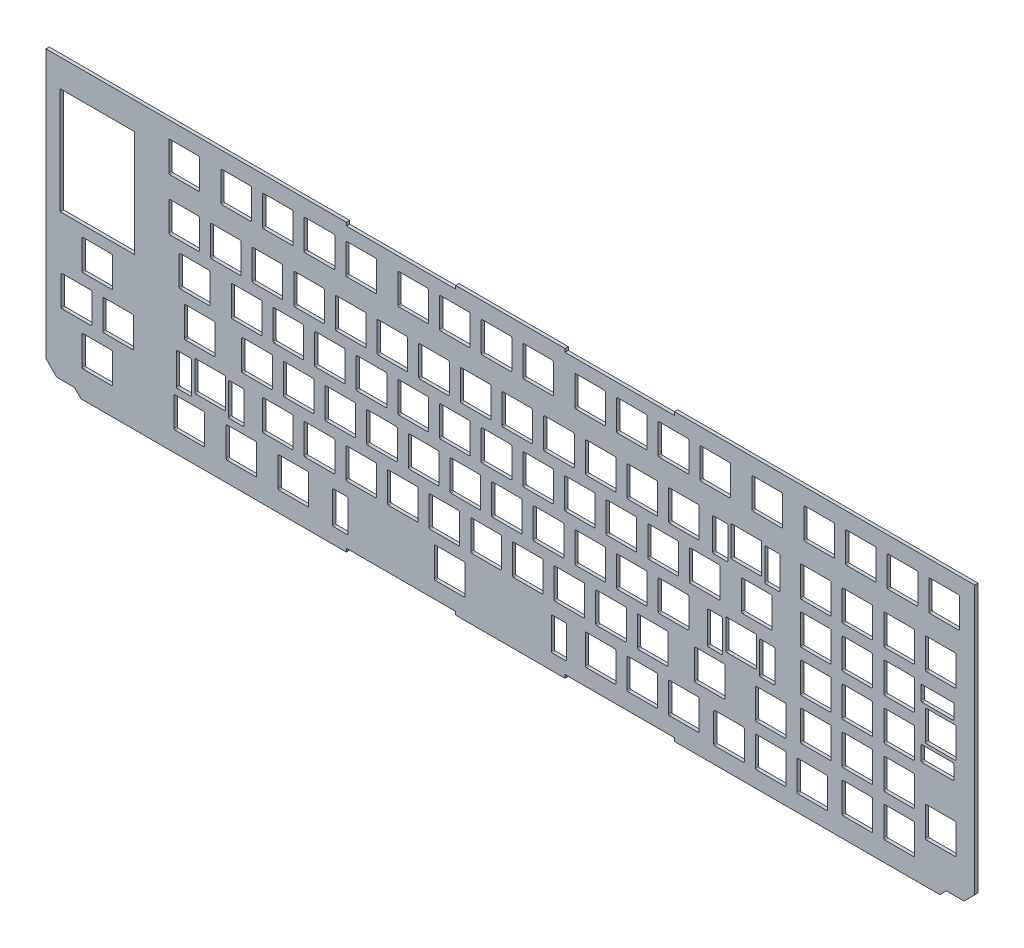
SolidWorks part; units mm, degrees
ref_plane "Přední rovina" through (0, 0, 0) normal (0, 0, 1) x (1, 0, 0)
ref_plane "Horní rovina" through (0, 0, 0) normal (0, 1, 0) x (1, 0, 0)
ref_plane "Pravá rovina" through (0, 0, 0) normal (1, 0, 0) x (0, 0, -1)
sketch "Model" plane through (0, 0, 0) normal (0, 0, 1) x (1, 0, 0)
  line L0 (53.8256, -2.525) -> (66.8256, -2.525)
  line L1 (53.8256, -16.525) -> (66.8256, -16.525)
  line L2 (53.3256, -3.025) -> (53.3256, -16.025)
  line L3 (67.3256, -3.025) -> (67.3256, -16.025)
  line L4 (77.6381, -2.525) -> (90.6381, -2.525)
  line L5 (77.6381, -16.525) -> (90.6381, -16.525)
  line L6 (77.1381, -3.025) -> (77.1381, -16.025)
  line L7 (91.1381, -3.025) -> (91.1381, -16.025)
  line L8 (96.6881, -2.525) -> (109.6881, -2.525)
  line L9 (96.6881, -16.525) -> (109.6881, -16.525)
  line L10 (96.1881, -3.025) -> (96.1881, -16.025)
  line L11 (110.1881, -3.025) -> (110.1881, -16.025)
  line L12 (115.7381, -2.525) -> (128.7381, -2.525)
  line L13 (115.7381, -16.525) -> (128.7381, -16.525)
  line L14 (115.2381, -3.025) -> (115.2381, -16.025)
  line L15 (129.2381, -3.025) -> (129.2381, -16.025)
  line L16 (134.7881, -2.525) -> (147.7881, -2.525)
  line L17 (134.7881, -16.525) -> (147.7881, -16.525)
  line L18 (134.2881, -3.025) -> (134.2881, -16.025)
  line L19 (148.2881, -3.025) -> (148.2881, -16.025)
  line L20 (158.6006, -2.525) -> (171.6006, -2.525)
  line L21 (158.6006, -16.525) -> (171.6006, -16.525)
  line L22 (158.1006, -3.025) -> (158.1006, -16.025)
  line L23 (172.1006, -3.025) -> (172.1006, -16.025)
  line L24 (177.6506, -2.525) -> (190.6506, -2.525)
  line L25 (177.6506, -16.525) -> (190.6506, -16.525)
  line L26 (177.1506, -3.025) -> (177.1506, -16.025)
  line L27 (191.1506, -3.025) -> (191.1506, -16.025)
  line L28 (196.7006, -2.525) -> (209.7006, -2.525)
  line L29 (196.7006, -16.525) -> (209.7006, -16.525)
  line L30 (196.2006, -3.025) -> (196.2006, -16.025)
  line L31 (210.2006, -3.025) -> (210.2006, -16.025)
  line L32 (215.7506, -2.525) -> (228.7506, -2.525)
  line L33 (215.7506, -16.525) -> (228.7506, -16.525)
  line L34 (215.2506, -3.025) -> (215.2506, -16.025)
  line L35 (229.2506, -3.025) -> (229.2506, -16.025)
  line L36 (239.5631, -2.525) -> (252.5631, -2.525)
  line L37 (239.5631, -16.525) -> (252.5631, -16.525)
  line L38 (239.0631, -3.025) -> (239.0631, -16.025)
  line L39 (253.0631, -3.025) -> (253.0631, -16.025)
  line L40 (258.6131, -2.525) -> (271.6131, -2.525)
  line L41 (258.6131, -16.525) -> (271.6131, -16.525)
  line L42 (258.1131, -3.025) -> (258.1131, -16.025)
  line L43 (272.1131, -3.025) -> (272.1131, -16.025)
  line L44 (277.6631, -2.525) -> (290.6631, -2.525)
  line L45 (277.6631, -16.525) -> (290.6631, -16.525)
  line L46 (277.1631, -3.025) -> (277.1631, -16.025)
  line L47 (291.1631, -3.025) -> (291.1631, -16.025)
  line L48 (296.7131, -2.525) -> (309.7131, -2.525)
  line L49 (296.7131, -16.525) -> (309.7131, -16.525)
  line L50 (296.2131, -3.025) -> (296.2131, -16.025)
  line L51 (310.2131, -3.025) -> (310.2131, -16.025)
  line L52 (320.5256, -2.525) -> (333.5256, -2.525)
  line L53 (320.5256, -16.525) -> (333.5256, -16.525)
  line L54 (320.0256, -3.025) -> (320.0256, -16.025)
  line L55 (334.0256, -3.025) -> (334.0256, -16.025)
  line L56 (344.3381, -2.525) -> (357.3381, -2.525)
  line L57 (344.3381, -16.525) -> (357.3381, -16.525)
  line L58 (343.8381, -3.025) -> (343.8381, -16.025)
  line L59 (357.8381, -3.025) -> (357.8381, -16.025)
  line L60 (363.3881, -2.525) -> (376.3881, -2.525)
  line L61 (363.3881, -16.525) -> (376.3881, -16.525)
  line L62 (362.8881, -3.025) -> (362.8881, -16.025)
  line L63 (376.8881, -3.025) -> (376.8881, -16.025)
  line L64 (382.4381, -2.525) -> (395.4381, -2.525)
  line L65 (382.4381, -16.525) -> (395.4381, -16.525)
  line L66 (381.9381, -3.025) -> (381.9381, -16.025)
  line L67 (395.9381, -3.025) -> (395.9381, -16.025)
  line L68 (401.4881, -2.525) -> (414.4881, -2.525)
  line L69 (401.4881, -16.525) -> (414.4881, -16.525)
  line L70 (400.9881, -3.025) -> (400.9881, -16.025)
  line L71 (414.9881, -3.025) -> (414.9881, -16.025)
  line L72 (53.8256, -26.3375) -> (66.8256, -26.3375)
  line L73 (53.8256, -40.3375) -> (66.8256, -40.3375)
  line L74 (53.3256, -26.8375) -> (53.3256, -39.8375)
  line L75 (67.3256, -26.8375) -> (67.3256, -39.8375)
  line L76 (72.8756, -26.3375) -> (85.8756, -26.3375)
  line L77 (72.8756, -40.3375) -> (85.8756, -40.3375)
  line L78 (72.3756, -26.8375) -> (72.3756, -39.8375)
  line L79 (86.3756, -26.8375) -> (86.3756, -39.8375)
  line L80 (91.9256, -26.3375) -> (104.9256, -26.3375)
  line L81 (91.9256, -40.3375) -> (104.9256, -40.3375)
  line L82 (91.4256, -26.8375) -> (91.4256, -39.8375)
  line L83 (105.4256, -26.8375) -> (105.4256, -39.8375)
  line L84 (110.9756, -26.3375) -> (123.9756, -26.3375)
  line L85 (110.9756, -40.3375) -> (123.9756, -40.3375)
  line L86 (110.4756, -26.8375) -> (110.4756, -39.8375)
  line L87 (124.4756, -26.8375) -> (124.4756, -39.8375)
  line L88 (130.0256, -26.3375) -> (143.0256, -26.3375)
  line L89 (130.0256, -40.3375) -> (143.0256, -40.3375)
  line L90 (129.5256, -26.8375) -> (129.5256, -39.8375)
  line L91 (143.5256, -26.8375) -> (143.5256, -39.8375)
  line L92 (149.0756, -26.3375) -> (162.0756, -26.3375)
  line L93 (149.0756, -40.3375) -> (162.0756, -40.3375)
  line L94 (148.5756, -26.8375) -> (148.5756, -39.8375)
  line L95 (162.5756, -26.8375) -> (162.5756, -39.8375)
  line L96 (168.1256, -26.3375) -> (181.1256, -26.3375)
  line L97 (168.1256, -40.3375) -> (181.1256, -40.3375)
  line L98 (167.6256, -26.8375) -> (167.6256, -39.8375)
  line L99 (181.6256, -26.8375) -> (181.6256, -39.8375)
  line L100 (187.1756, -26.3375) -> (200.1756, -26.3375)
  line L101 (187.1756, -40.3375) -> (200.1756, -40.3375)
  line L102 (186.6756, -26.8375) -> (186.6756, -39.8375)
  line L103 (200.6756, -26.8375) -> (200.6756, -39.8375)
  line L104 (206.2256, -26.3375) -> (219.2256, -26.3375)
  line L105 (206.2256, -40.3375) -> (219.2256, -40.3375)
  line L106 (205.7256, -26.8375) -> (205.7256, -39.8375)
  line L107 (219.7256, -26.8375) -> (219.7256, -39.8375)
  line L108 (225.2756, -26.3375) -> (238.2756, -26.3375)
  line L109 (225.2756, -40.3375) -> (238.2756, -40.3375)
  line L110 (224.7756, -26.8375) -> (224.7756, -39.8375)
  line L111 (238.7756, -26.8375) -> (238.7756, -39.8375)
  line L112 (244.3256, -26.3375) -> (257.3256, -26.3375)
  line L113 (244.3256, -40.3375) -> (257.3256, -40.3375)
  line L114 (243.8256, -26.8375) -> (243.8256, -39.8375)
  line L115 (257.8256, -26.8375) -> (257.8256, -39.8375)
  line L116 (263.3756, -26.3375) -> (276.3756, -26.3375)
  line L117 (263.3756, -40.3375) -> (276.3756, -40.3375)
  line L118 (262.8756, -26.8375) -> (262.8756, -39.8375)
  line L119 (276.8756, -26.8375) -> (276.8756, -39.8375)
  line L120 (282.4256, -26.3375) -> (295.4256, -26.3375)
  line L121 (282.4256, -40.3375) -> (295.4256, -40.3375)
  line L122 (281.9256, -26.8375) -> (281.9256, -39.8375)
  line L123 (295.9256, -26.8375) -> (295.9256, -39.8375)
  line L124 (311.0006, -26.3375) -> (324.0006, -26.3375)
  line L125 (311.0006, -40.3375) -> (324.0006, -40.3375)
  line L126 (310.5006, -26.8375) -> (310.5006, -39.8375)
  line L127 (324.5006, -26.8375) -> (324.5006, -39.8375)
  line L128 (302.5626, -27.3375) -> (308.5626, -27.3375)
  line L129 (302.5626, -42.3375) -> (308.5626, -42.3375)
  line L130 (302.0626, -27.8375) -> (302.0626, -41.8375)
  line L131 (309.0626, -27.8375) -> (309.0626, -41.8375)
  line L132 (326.4386, -27.3375) -> (332.4386, -27.3375)
  line L133 (326.4386, -42.3375) -> (332.4386, -42.3375)
  line L134 (325.9386, -27.8375) -> (325.9386, -41.8375)
  line L135 (332.9386, -27.8375) -> (332.9386, -41.8375)
  line L136 (342.7513, -26.3375) -> (355.7513, -26.3375)
  line L137 (342.7513, -40.3375) -> (355.7513, -40.3375)
  line L138 (342.2513, -26.8375) -> (342.2513, -39.8375)
  line L139 (356.2513, -26.8375) -> (356.2513, -39.8375)
  line L140 (361.8013, -26.3375) -> (374.8013, -26.3375)
  line L141 (361.8013, -40.3375) -> (374.8013, -40.3375)
  line L142 (361.3013, -26.8375) -> (361.3013, -39.8375)
  line L143 (375.3013, -26.8375) -> (375.3013, -39.8375)
  line L144 (380.8513, -26.3375) -> (393.8513, -26.3375)
  line L145 (380.8513, -40.3375) -> (393.8513, -40.3375)
  line L146 (380.3513, -26.8375) -> (380.3513, -39.8375)
  line L147 (394.3513, -26.8375) -> (394.3513, -39.8375)
  line L148 (399.9013, -26.3375) -> (412.9013, -26.3375)
  line L149 (399.9013, -40.3375) -> (412.9013, -40.3375)
  line L150 (399.4013, -26.8375) -> (399.4013, -39.8375)
  line L151 (413.4013, -26.8375) -> (413.4013, -39.8375)
  line L152 (58.5881, -45.3875) -> (71.5881, -45.3875)
  line L153 (58.5881, -59.3875) -> (71.5881, -59.3875)
  line L154 (58.0881, -45.8875) -> (58.0881, -58.8875)
  line L155 (72.0881, -45.8875) -> (72.0881, -58.8875)
  line L156 (82.4006, -45.3875) -> (95.4006, -45.3875)
  line L157 (82.4006, -59.3875) -> (95.4006, -59.3875)
  line L158 (81.9006, -45.8875) -> (81.9006, -58.8875)
  line L159 (95.9006, -45.8875) -> (95.9006, -58.8875)
  line L160 (101.4506, -45.3875) -> (114.4506, -45.3875)
  line L161 (101.4506, -59.3875) -> (114.4506, -59.3875)
  line L162 (100.9506, -45.8875) -> (100.9506, -58.8875)
  line L163 (114.9506, -45.8875) -> (114.9506, -58.8875)
  line L164 (120.5006, -45.3875) -> (133.5006, -45.3875)
  line L165 (120.5006, -59.3875) -> (133.5006, -59.3875)
  line L166 (120.0006, -45.8875) -> (120.0006, -58.8875)
  line L167 (134.0006, -45.8875) -> (134.0006, -58.8875)
  line L168 (139.5506, -45.3875) -> (152.5506, -45.3875)
  line L169 (139.5506, -59.3875) -> (152.5506, -59.3875)
  line L170 (139.0506, -45.8875) -> (139.0506, -58.8875)
  line L171 (153.0506, -45.8875) -> (153.0506, -58.8875)
  line L172 (158.6006, -45.3875) -> (171.6006, -45.3875)
  line L173 (158.6006, -59.3875) -> (171.6006, -59.3875)
  line L174 (158.1006, -45.8875) -> (158.1006, -58.8875)
  line L175 (172.1006, -45.8875) -> (172.1006, -58.8875)
  line L176 (177.6506, -45.3875) -> (190.6506, -45.3875)
  line L177 (177.6506, -59.3875) -> (190.6506, -59.3875)
  line L178 (177.1506, -45.8875) -> (177.1506, -58.8875)
  line L179 (191.1506, -45.8875) -> (191.1506, -58.8875)
  line L180 (196.7006, -45.3875) -> (209.7006, -45.3875)
  line L181 (196.7006, -59.3875) -> (209.7006, -59.3875)
  line L182 (196.2006, -45.8875) -> (196.2006, -58.8875)
  line L183 (210.2006, -45.8875) -> (210.2006, -58.8875)
  line L184 (215.7506, -45.3875) -> (228.7506, -45.3875)
  line L185 (215.7506, -59.3875) -> (228.7506, -59.3875)
  line L186 (215.2506, -45.8875) -> (215.2506, -58.8875)
  line L187 (229.2506, -45.8875) -> (229.2506, -58.8875)
  line L188 (234.8006, -45.3875) -> (247.8006, -45.3875)
  line L189 (234.8006, -59.3875) -> (247.8006, -59.3875)
  line L190 (234.3006, -45.8875) -> (234.3006, -58.8875)
  line L191 (248.3006, -45.8875) -> (248.3006, -58.8875)
  line L192 (253.8506, -45.3875) -> (266.8506, -45.3875)
  line L193 (253.8506, -59.3875) -> (266.8506, -59.3875)
  line L194 (253.3506, -45.8875) -> (253.3506, -58.8875)
  line L195 (267.3506, -45.8875) -> (267.3506, -58.8875)
  line L196 (272.9006, -45.3875) -> (285.9006, -45.3875)
  line L197 (272.9006, -59.3875) -> (285.9006, -59.3875)
  line L198 (272.4006, -45.8875) -> (272.4006, -58.8875)
  line L199 (286.4006, -45.8875) -> (286.4006, -58.8875)
  line L200 (291.9506, -45.3875) -> (304.9506, -45.3875)
  line L201 (291.9506, -59.3875) -> (304.9506, -59.3875)
  line L202 (291.4506, -45.8875) -> (291.4506, -58.8875)
  line L203 (305.4506, -45.8875) -> (305.4506, -58.8875)
  line L204 (315.7631, -45.3875) -> (328.7631, -45.3875)
  line L205 (315.7631, -59.3875) -> (328.7631, -59.3875)
  line L206 (315.2631, -45.8875) -> (315.2631, -58.8875)
  line L207 (329.2631, -45.8875) -> (329.2631, -58.8875)
  line L208 (342.7513, -45.3875) -> (355.7513, -45.3875)
  line L209 (342.7513, -59.3875) -> (355.7513, -59.3875)
  line L210 (342.2513, -45.8875) -> (342.2513, -58.8875)
  line L211 (356.2513, -45.8875) -> (356.2513, -58.8875)
  line L212 (361.8013, -45.3875) -> (374.8013, -45.3875)
  line L213 (361.8013, -59.3875) -> (374.8013, -59.3875)
  line L214 (361.3013, -45.8875) -> (361.3013, -58.8875)
  line L215 (375.3013, -45.8875) -> (375.3013, -58.8875)
  line L216 (380.8513, -45.3875) -> (393.8513, -45.3875)
  line L217 (380.8513, -59.3875) -> (393.8513, -59.3875)
  line L218 (380.3513, -45.8875) -> (380.3513, -58.8875)
  line L219 (394.3513, -45.8875) -> (394.3513, -58.8875)
  line L220 (413.4013, -55.4125) -> (413.4013, -68.4125)
  line L221 (399.4013, -55.4125) -> (399.4013, -68.4125)
  line L222 (412.9013, -54.9125) -> (399.9013, -54.9125)
  line L223 (412.9013, -68.9125) -> (399.9013, -68.9125)
  line L224 (412.4013, -46.9745) -> (412.4013, -52.9745)
  line L225 (397.4013, -46.9745) -> (397.4013, -52.9745)
  line L226 (411.9013, -46.4745) -> (397.9013, -46.4745)
  line L227 (411.9013, -53.4745) -> (397.9013, -53.4745)
  line L228 (412.4013, -70.8505) -> (412.4013, -76.8505)
  line L229 (397.4013, -70.8505) -> (397.4013, -76.8505)
  line L230 (411.9013, -70.3505) -> (397.9013, -70.3505)
  line L231 (411.9013, -77.3505) -> (397.9013, -77.3505)
  line L232 (14.1369, -61.2619) -> (27.1369, -61.2619)
  line L233 (14.1369, -75.2619) -> (27.1369, -75.2619)
  line L234 (13.6369, -61.7619) -> (13.6369, -74.7619)
  line L235 (27.6369, -61.7619) -> (27.6369, -74.7619)
  line L236 (60.9694, -64.4375) -> (73.9694, -64.4375)
  line L237 (60.9694, -78.4375) -> (73.9694, -78.4375)
  line L238 (60.4694, -64.9375) -> (60.4694, -77.9375)
  line L239 (74.4694, -64.9375) -> (74.4694, -77.9375)
  line L240 (87.1631, -64.4375) -> (100.1631, -64.4375)
  line L241 (87.1631, -78.4375) -> (100.1631, -78.4375)
  line L242 (86.6631, -64.9375) -> (86.6631, -77.9375)
  line L243 (100.6631, -64.9375) -> (100.6631, -77.9375)
  line L244 (106.2131, -64.4375) -> (119.2131, -64.4375)
  line L245 (106.2131, -78.4375) -> (119.2131, -78.4375)
  line L246 (105.7131, -64.9375) -> (105.7131, -77.9375)
  line L247 (119.7131, -64.9375) -> (119.7131, -77.9375)
  line L248 (125.2631, -64.4375) -> (138.2631, -64.4375)
  line L249 (125.2631, -78.4375) -> (138.2631, -78.4375)
  line L250 (124.7631, -64.9375) -> (124.7631, -77.9375)
  line L251 (138.7631, -64.9375) -> (138.7631, -77.9375)
  line L252 (144.3131, -64.4375) -> (157.3131, -64.4375)
  line L253 (144.3131, -78.4375) -> (157.3131, -78.4375)
  line L254 (143.8131, -64.9375) -> (143.8131, -77.9375)
  line L255 (157.8131, -64.9375) -> (157.8131, -77.9375)
  line L256 (163.3631, -64.4375) -> (176.3631, -64.4375)
  line L257 (163.3631, -78.4375) -> (176.3631, -78.4375)
  line L258 (162.8631, -64.9375) -> (162.8631, -77.9375)
  line L259 (176.8631, -64.9375) -> (176.8631, -77.9375)
  line L260 (182.4131, -64.4375) -> (195.4131, -64.4375)
  line L261 (182.4131, -78.4375) -> (195.4131, -78.4375)
  line L262 (181.9131, -64.9375) -> (181.9131, -77.9375)
  line L263 (195.9131, -64.9375) -> (195.9131, -77.9375)
  line L264 (201.4631, -64.4375) -> (214.4631, -64.4375)
  line L265 (201.4631, -78.4375) -> (214.4631, -78.4375)
  line L266 (200.9631, -64.9375) -> (200.9631, -77.9375)
  line L267 (214.9631, -64.9375) -> (214.9631, -77.9375)
  line L268 (220.5131, -64.4375) -> (233.5131, -64.4375)
  line L269 (220.5131, -78.4375) -> (233.5131, -78.4375)
  line L270 (220.0131, -64.9375) -> (220.0131, -77.9375)
  line L271 (234.0131, -64.9375) -> (234.0131, -77.9375)
  line L272 (239.5631, -64.4375) -> (252.5631, -64.4375)
  line L273 (239.5631, -78.4375) -> (252.5631, -78.4375)
  line L274 (239.0631, -64.9375) -> (239.0631, -77.9375)
  line L275 (253.0631, -64.9375) -> (253.0631, -77.9375)
  line L276 (258.6131, -64.4375) -> (271.6131, -64.4375)
  line L277 (258.6131, -78.4375) -> (271.6131, -78.4375)
  line L278 (258.1131, -64.9375) -> (258.1131, -77.9375)
  line L279 (272.1131, -64.9375) -> (272.1131, -77.9375)
  line L280 (277.6631, -64.4375) -> (290.6631, -64.4375)
  line L281 (277.6631, -78.4375) -> (290.6631, -78.4375)
  line L282 (277.1631, -64.9375) -> (277.1631, -77.9375)
  line L283 (291.1631, -64.9375) -> (291.1631, -77.9375)
  line L284 (308.6194, -64.4375) -> (321.6194, -64.4375)
  line L285 (308.6194, -78.4375) -> (321.6194, -78.4375)
  line L286 (308.1194, -64.9375) -> (308.1194, -77.9375)
  line L287 (322.1194, -64.9375) -> (322.1194, -77.9375)
  line L288 (300.1814, -65.4375) -> (306.1814, -65.4375)
  line L289 (300.1814, -80.4375) -> (306.1814, -80.4375)
  line L290 (299.6814, -65.9375) -> (299.6814, -79.9375)
  line L291 (306.6814, -65.9375) -> (306.6814, -79.9375)
  line L292 (324.0574, -65.4375) -> (330.0574, -65.4375)
  line L293 (324.0574, -80.4375) -> (330.0574, -80.4375)
  line L294 (323.5574, -65.9375) -> (323.5574, -79.9375)
  line L295 (330.5574, -65.9375) -> (330.5574, -79.9375)
  line L296 (342.7513, -64.4375) -> (355.7513, -64.4375)
  line L297 (342.7513, -78.4375) -> (355.7513, -78.4375)
  line L298 (342.2513, -64.9375) -> (342.2513, -77.9375)
  line L299 (356.2513, -64.9375) -> (356.2513, -77.9375)
  line L300 (361.8013, -64.4375) -> (374.8013, -64.4375)
  line L301 (361.8013, -78.4375) -> (374.8013, -78.4375)
  line L302 (361.3013, -64.9375) -> (361.3013, -77.9375)
  line L303 (375.3013, -64.9375) -> (375.3013, -77.9375)
  line L304 (380.8513, -64.4375) -> (393.8513, -64.4375)
  line L305 (380.8513, -78.4375) -> (393.8513, -78.4375)
  line L306 (380.3513, -64.9375) -> (380.3513, -77.9375)
  line L307 (394.3513, -64.9375) -> (394.3513, -77.9375)
  line L308 (4.6119, -80.3119) -> (17.6119, -80.3119)
  line L309 (4.6119, -94.3119) -> (17.6119, -94.3119)
  line L310 (4.1119, -80.8119) -> (4.1119, -93.8119)
  line L311 (18.1119, -80.8119) -> (18.1119, -93.8119)
  line L312 (23.6619, -80.3119) -> (36.6619, -80.3119)
  line L313 (23.6619, -94.3119) -> (36.6619, -94.3119)
  line L314 (23.1619, -80.8119) -> (23.1619, -93.8119)
  line L315 (37.1619, -80.8119) -> (37.1619, -93.8119)
  line L316 (65.7319, -83.4875) -> (78.7319, -83.4875)
  line L317 (65.7319, -97.4875) -> (78.7319, -97.4875)
  line L318 (65.2319, -83.9875) -> (65.2319, -96.9875)
  line L319 (79.2319, -83.9875) -> (79.2319, -96.9875)
  line L320 (57.2939, -84.4875) -> (63.2939, -84.4875)
  line L321 (57.2939, -99.4875) -> (63.2939, -99.4875)
  line L322 (56.7939, -84.9875) -> (56.7939, -98.9875)
  line L323 (63.7939, -84.9875) -> (63.7939, -98.9875)
  line L324 (81.1699, -84.4875) -> (87.1699, -84.4875)
  line L325 (81.1699, -99.4875) -> (87.1699, -99.4875)
  line L326 (80.6699, -84.9875) -> (80.6699, -98.9875)
  line L327 (87.6699, -84.9875) -> (87.6699, -98.9875)
  line L328 (96.6881, -83.4875) -> (109.6881, -83.4875)
  line L329 (96.6881, -97.4875) -> (109.6881, -97.4875)
  line L330 (96.1881, -83.9875) -> (96.1881, -96.9875)
  line L331 (110.1881, -83.9875) -> (110.1881, -96.9875)
  line L332 (115.7381, -83.4875) -> (128.7381, -83.4875)
  line L333 (115.7381, -97.4875) -> (128.7381, -97.4875)
  line L334 (115.2381, -83.9875) -> (115.2381, -96.9875)
  line L335 (129.2381, -83.9875) -> (129.2381, -96.9875)
  line L336 (134.7881, -83.4875) -> (147.7881, -83.4875)
  line L337 (134.7881, -97.4875) -> (147.7881, -97.4875)
  line L338 (134.2881, -83.9875) -> (134.2881, -96.9875)
  line L339 (148.2881, -83.9875) -> (148.2881, -96.9875)
  line L340 (153.8381, -83.4875) -> (166.8381, -83.4875)
  line L341 (153.8381, -97.4875) -> (166.8381, -97.4875)
  line L342 (153.3381, -83.9875) -> (153.3381, -96.9875)
  line L343 (167.3381, -83.9875) -> (167.3381, -96.9875)
  line L344 (172.8881, -83.4875) -> (185.8881, -83.4875)
  line L345 (172.8881, -97.4875) -> (185.8881, -97.4875)
  line L346 (172.3881, -83.9875) -> (172.3881, -96.9875)
  line L347 (186.3881, -83.9875) -> (186.3881, -96.9875)
  line L348 (191.9381, -83.4875) -> (204.9381, -83.4875)
  line L349 (191.9381, -97.4875) -> (204.9381, -97.4875)
  line L350 (191.4381, -83.9875) -> (191.4381, -96.9875)
  line L351 (205.4381, -83.9875) -> (205.4381, -96.9875)
  line L352 (210.9881, -83.4875) -> (223.9881, -83.4875)
  line L353 (210.9881, -97.4875) -> (223.9881, -97.4875)
  line L354 (210.4881, -83.9875) -> (210.4881, -96.9875)
  line L355 (224.4881, -83.9875) -> (224.4881, -96.9875)
  line L356 (230.0381, -83.4875) -> (243.0381, -83.4875)
  line L357 (230.0381, -97.4875) -> (243.0381, -97.4875)
  line L358 (229.5381, -83.9875) -> (229.5381, -96.9875)
  line L359 (243.5381, -83.9875) -> (243.5381, -96.9875)
  line L360 (249.0881, -83.4875) -> (262.0881, -83.4875)
  line L361 (249.0881, -97.4875) -> (262.0881, -97.4875)
  line L362 (248.5881, -83.9875) -> (248.5881, -96.9875)
  line L363 (262.5881, -83.9875) -> (262.5881, -96.9875)
  line L364 (268.1381, -83.4875) -> (281.1381, -83.4875)
  line L365 (268.1381, -97.4875) -> (281.1381, -97.4875)
  line L366 (267.6381, -83.9875) -> (267.6381, -96.9875)
  line L367 (281.6381, -83.9875) -> (281.6381, -96.9875)
  line L368 (294.3319, -83.4875) -> (307.3319, -83.4875)
  line L369 (294.3319, -97.4875) -> (307.3319, -97.4875)
  line L370 (293.8319, -83.9875) -> (293.8319, -96.9875)
  line L371 (307.8319, -83.9875) -> (307.8319, -96.9875)
  line L372 (342.7513, -83.4875) -> (355.7513, -83.4875)
  line L373 (342.7513, -97.4875) -> (355.7513, -97.4875)
  line L374 (342.2513, -83.9875) -> (342.2513, -96.9875)
  line L375 (356.2513, -83.9875) -> (356.2513, -96.9875)
  line L376 (361.8013, -83.4875) -> (374.8013, -83.4875)
  line L377 (361.8013, -97.4875) -> (374.8013, -97.4875)
  line L378 (361.3013, -83.9875) -> (361.3013, -96.9875)
  line L379 (375.3013, -83.9875) -> (375.3013, -96.9875)
  line L380 (380.8513, -83.4875) -> (393.8513, -83.4875)
  line L381 (380.8513, -97.4875) -> (393.8513, -97.4875)
  line L382 (380.3513, -83.9875) -> (380.3513, -96.9875)
  line L383 (394.3513, -83.9875) -> (394.3513, -96.9875)
  line L384 (413.4013, -93.5125) -> (413.4013, -106.5125)
  line L385 (399.4013, -93.5125) -> (399.4013, -106.5125)
  line L386 (412.9013, -93.0125) -> (399.9013, -93.0125)
  line L387 (412.9013, -107.0125) -> (399.9013, -107.0125)
  line L396 (322.1125, -85.0744) -> (335.1125, -85.0744)
  line L397 (322.1125, -99.0744) -> (335.1125, -99.0744)
  line L398 (321.6125, -85.5744) -> (321.6125, -98.5744)
  line L399 (335.6125, -85.5744) -> (335.6125, -98.5744)
  line L400 (14.1369, -99.3619) -> (27.1369, -99.3619)
  line L401 (14.1369, -113.3619) -> (27.1369, -113.3619)
  line L402 (13.6369, -99.8619) -> (13.6369, -112.8619)
  line L403 (27.6369, -99.8619) -> (27.6369, -112.8619)
  line L404 (56.2069, -102.5375) -> (69.2069, -102.5375)
  line L405 (56.2069, -116.5375) -> (69.2069, -116.5375)
  line L406 (55.7069, -103.0375) -> (55.7069, -116.0375)
  line L407 (69.7069, -103.0375) -> (69.7069, -116.0375)
  line L408 (80.0194, -102.5375) -> (93.0194, -102.5375)
  line L409 (80.0194, -116.5375) -> (93.0194, -116.5375)
  line L410 (79.5194, -103.0375) -> (79.5194, -116.0375)
  line L411 (93.5194, -103.0375) -> (93.5194, -116.0375)
  line L412 (103.8319, -102.5375) -> (116.8319, -102.5375)
  line L413 (103.8319, -116.5375) -> (116.8319, -116.5375)
  line L414 (103.3319, -103.0375) -> (103.3319, -116.0375)
  line L415 (117.3319, -103.0375) -> (117.3319, -116.0375)
  line L416 (175.2694, -102.5375) -> (188.2694, -102.5375)
  line L417 (175.2694, -116.5375) -> (188.2694, -116.5375)
  line L418 (174.7694, -103.0375) -> (174.7694, -116.0375)
  line L419 (188.7694, -103.0375) -> (188.7694, -116.0375)
  line L420 (128.7694, -103.5375) -> (134.7694, -103.5375)
  line L421 (128.7694, -118.5375) -> (134.7694, -118.5375)
  line L422 (128.2694, -104.0375) -> (128.2694, -118.0375)
  line L423 (135.2694, -104.0375) -> (135.2694, -118.0375)
  line L424 (228.7694, -103.5375) -> (234.7694, -103.5375)
  line L425 (228.7694, -118.5375) -> (234.7694, -118.5375)
  line L426 (228.2694, -104.0375) -> (228.2694, -118.0375)
  line L427 (235.2694, -104.0375) -> (235.2694, -118.0375)
  line L428 (244.3256, -102.5375) -> (257.3256, -102.5375)
  line L429 (244.3256, -116.5375) -> (257.3256, -116.5375)
  line L430 (243.8256, -103.0375) -> (243.8256, -116.0375)
  line L431 (257.8256, -103.0375) -> (257.8256, -116.0375)
  line L432 (263.3756, -102.5375) -> (276.3756, -102.5375)
  line L433 (263.3756, -116.5375) -> (276.3756, -116.5375)
  line L434 (262.8756, -103.0375) -> (262.8756, -116.0375)
  line L435 (276.8756, -103.0375) -> (276.8756, -116.0375)
  line L436 (282.4256, -102.5375) -> (295.4256, -102.5375)
  line L437 (282.4256, -116.5375) -> (295.4256, -116.5375)
  line L438 (281.9256, -103.0375) -> (281.9256, -116.0375)
  line L439 (295.9256, -103.0375) -> (295.9256, -116.0375)
  line L440 (361.8013, -102.5375) -> (374.8013, -102.5375)
  line L441 (361.8013, -116.5375) -> (374.8013, -116.5375)
  line L442 (361.3013, -103.0375) -> (361.3013, -116.0375)
  line L443 (375.3013, -103.0375) -> (375.3013, -116.0375)
  line L444 (380.8513, -102.5375) -> (393.8513, -102.5375)
  line L445 (380.8513, -116.5375) -> (393.8513, -116.5375)
  line L446 (380.3513, -103.0375) -> (380.3513, -116.0375)
  line L447 (394.3513, -103.0375) -> (394.3513, -116.0375)
  line L448 (303.0625, -104.1244) -> (316.0625, -104.1244)
  line L449 (303.0625, -118.1244) -> (316.0625, -118.1244)
  line L450 (302.5625, -104.6244) -> (302.5625, -117.6244)
  line L451 (316.5625, -104.6244) -> (316.5625, -117.6244)
  line L452 (322.1125, -104.1244) -> (335.1125, -104.1244)
  line L453 (322.1125, -118.1244) -> (335.1125, -118.1244)
  line L454 (321.6125, -104.6244) -> (321.6125, -117.6244)
  line L455 (335.6125, -104.6244) -> (335.6125, -117.6244)
  line L456 (341.1625, -104.1244) -> (354.1625, -104.1244)
  line L457 (341.1625, -118.1244) -> (354.1625, -118.1244)
  line L458 (340.6625, -104.6244) -> (340.6625, -117.6244)
  line L459 (354.6625, -104.6244) -> (354.6625, -117.6244)
  line L460 (1.5869, -120.6494) -> (417.5131, -120.6494)
  line L461 (1.5869, 0) -> (417.5131, 0)
  line L462 (1.5869, -120.6494) -> (1.5869, 0)
  line L463 (417.5131, -120.6494) -> (417.5131, 0)
  arc A0 (53.8256, -2.525) -> (53.3256, -3.025) centre (53.8256, -3.025) ccw
  arc A1 (67.3256, -3.025) -> (66.8256, -2.525) centre (66.8256, -3.025) ccw
  arc A2 (53.3256, -16.025) -> (53.8256, -16.525) centre (53.8256, -16.025) ccw
  arc A3 (66.8256, -16.525) -> (67.3256, -16.025) centre (66.8256, -16.025) ccw
  arc A4 (77.6381, -2.525) -> (77.1381, -3.025) centre (77.6381, -3.025) ccw
  arc A5 (91.1381, -3.025) -> (90.6381, -2.525) centre (90.6381, -3.025) ccw
  arc A6 (77.1381, -16.025) -> (77.6381, -16.525) centre (77.6381, -16.025) ccw
  arc A7 (90.6381, -16.525) -> (91.1381, -16.025) centre (90.6381, -16.025) ccw
  arc A8 (96.6881, -2.525) -> (96.1881, -3.025) centre (96.6881, -3.025) ccw
  arc A9 (110.1881, -3.025) -> (109.6881, -2.525) centre (109.6881, -3.025) ccw
  arc A10 (96.1881, -16.025) -> (96.6881, -16.525) centre (96.6881, -16.025) ccw
  arc A11 (109.6881, -16.525) -> (110.1881, -16.025) centre (109.6881, -16.025) ccw
  arc A12 (115.7381, -2.525) -> (115.2381, -3.025) centre (115.7381, -3.025) ccw
  arc A13 (129.2381, -3.025) -> (128.7381, -2.525) centre (128.7381, -3.025) ccw
  arc A14 (115.2381, -16.025) -> (115.7381, -16.525) centre (115.7381, -16.025) ccw
  arc A15 (128.7381, -16.525) -> (129.2381, -16.025) centre (128.7381, -16.025) ccw
  arc A16 (134.7881, -2.525) -> (134.2881, -3.025) centre (134.7881, -3.025) ccw
  arc A17 (148.2881, -3.025) -> (147.7881, -2.525) centre (147.7881, -3.025) ccw
  arc A18 (134.2881, -16.025) -> (134.7881, -16.525) centre (134.7881, -16.025) ccw
  arc A19 (147.7881, -16.525) -> (148.2881, -16.025) centre (147.7881, -16.025) ccw
  arc A20 (158.6006, -2.525) -> (158.1006, -3.025) centre (158.6006, -3.025) ccw
  arc A21 (172.1006, -3.025) -> (171.6006, -2.525) centre (171.6006, -3.025) ccw
  arc A22 (158.1006, -16.025) -> (158.6006, -16.525) centre (158.6006, -16.025) ccw
  arc A23 (171.6006, -16.525) -> (172.1006, -16.025) centre (171.6006, -16.025) ccw
  arc A24 (177.6506, -2.525) -> (177.1506, -3.025) centre (177.6506, -3.025) ccw
  arc A25 (191.1506, -3.025) -> (190.6506, -2.525) centre (190.6506, -3.025) ccw
  arc A26 (177.1506, -16.025) -> (177.6506, -16.525) centre (177.6506, -16.025) ccw
  arc A27 (190.6506, -16.525) -> (191.1506, -16.025) centre (190.6506, -16.025) ccw
  arc A28 (196.7006, -2.525) -> (196.2006, -3.025) centre (196.7006, -3.025) ccw
  arc A29 (210.2006, -3.025) -> (209.7006, -2.525) centre (209.7006, -3.025) ccw
  arc A30 (196.2006, -16.025) -> (196.7006, -16.525) centre (196.7006, -16.025) ccw
  arc A31 (209.7006, -16.525) -> (210.2006, -16.025) centre (209.7006, -16.025) ccw
  arc A32 (215.7506, -2.525) -> (215.2506, -3.025) centre (215.7506, -3.025) ccw
  arc A33 (229.2506, -3.025) -> (228.7506, -2.525) centre (228.7506, -3.025) ccw
  arc A34 (215.2506, -16.025) -> (215.7506, -16.525) centre (215.7506, -16.025) ccw
  arc A35 (228.7506, -16.525) -> (229.2506, -16.025) centre (228.7506, -16.025) ccw
  arc A36 (239.5631, -2.525) -> (239.0631, -3.025) centre (239.5631, -3.025) ccw
  arc A37 (253.0631, -3.025) -> (252.5631, -2.525) centre (252.5631, -3.025) ccw
  arc A38 (239.0631, -16.025) -> (239.5631, -16.525) centre (239.5631, -16.025) ccw
  arc A39 (252.5631, -16.525) -> (253.0631, -16.025) centre (252.5631, -16.025) ccw
  arc A40 (258.6131, -2.525) -> (258.1131, -3.025) centre (258.6131, -3.025) ccw
  arc A41 (272.1131, -3.025) -> (271.6131, -2.525) centre (271.6131, -3.025) ccw
  arc A42 (258.1131, -16.025) -> (258.6131, -16.525) centre (258.6131, -16.025) ccw
  arc A43 (271.6131, -16.525) -> (272.1131, -16.025) centre (271.6131, -16.025) ccw
  arc A44 (277.6631, -2.525) -> (277.1631, -3.025) centre (277.6631, -3.025) ccw
  arc A45 (291.1631, -3.025) -> (290.6631, -2.525) centre (290.6631, -3.025) ccw
  arc A46 (277.1631, -16.025) -> (277.6631, -16.525) centre (277.6631, -16.025) ccw
  arc A47 (290.6631, -16.525) -> (291.1631, -16.025) centre (290.6631, -16.025) ccw
  arc A48 (296.7131, -2.525) -> (296.2131, -3.025) centre (296.7131, -3.025) ccw
  arc A49 (310.2131, -3.025) -> (309.7131, -2.525) centre (309.7131, -3.025) ccw
  arc A50 (296.2131, -16.025) -> (296.7131, -16.525) centre (296.7131, -16.025) ccw
  arc A51 (309.7131, -16.525) -> (310.2131, -16.025) centre (309.7131, -16.025) ccw
  arc A52 (320.5256, -2.525) -> (320.0256, -3.025) centre (320.5256, -3.025) ccw
  arc A53 (334.0256, -3.025) -> (333.5256, -2.525) centre (333.5256, -3.025) ccw
  arc A54 (320.0256, -16.025) -> (320.5256, -16.525) centre (320.5256, -16.025) ccw
  arc A55 (333.5256, -16.525) -> (334.0256, -16.025) centre (333.5256, -16.025) ccw
  arc A56 (344.3381, -2.525) -> (343.8381, -3.025) centre (344.3381, -3.025) ccw
  arc A57 (357.8381, -3.025) -> (357.3381, -2.525) centre (357.3381, -3.025) ccw
  arc A58 (343.8381, -16.025) -> (344.3381, -16.525) centre (344.3381, -16.025) ccw
  arc A59 (357.3381, -16.525) -> (357.8381, -16.025) centre (357.3381, -16.025) ccw
  arc A60 (363.3881, -2.525) -> (362.8881, -3.025) centre (363.3881, -3.025) ccw
  arc A61 (376.8881, -3.025) -> (376.3881, -2.525) centre (376.3881, -3.025) ccw
  arc A62 (362.8881, -16.025) -> (363.3881, -16.525) centre (363.3881, -16.025) ccw
  arc A63 (376.3881, -16.525) -> (376.8881, -16.025) centre (376.3881, -16.025) ccw
  arc A64 (382.4381, -2.525) -> (381.9381, -3.025) centre (382.4381, -3.025) ccw
  arc A65 (395.9381, -3.025) -> (395.4381, -2.525) centre (395.4381, -3.025) ccw
  arc A66 (381.9381, -16.025) -> (382.4381, -16.525) centre (382.4381, -16.025) ccw
  arc A67 (395.4381, -16.525) -> (395.9381, -16.025) centre (395.4381, -16.025) ccw
  arc A68 (401.4881, -2.525) -> (400.9881, -3.025) centre (401.4881, -3.025) ccw
  arc A69 (414.9881, -3.025) -> (414.4881, -2.525) centre (414.4881, -3.025) ccw
  arc A70 (400.9881, -16.025) -> (401.4881, -16.525) centre (401.4881, -16.025) ccw
  arc A71 (414.4881, -16.525) -> (414.9881, -16.025) centre (414.4881, -16.025) ccw
  arc A72 (53.8256, -26.3375) -> (53.3256, -26.8375) centre (53.8256, -26.8375) ccw
  arc A73 (67.3256, -26.8375) -> (66.8256, -26.3375) centre (66.8256, -26.8375) ccw
  arc A74 (53.3256, -39.8375) -> (53.8256, -40.3375) centre (53.8256, -39.8375) ccw
  arc A75 (66.8256, -40.3375) -> (67.3256, -39.8375) centre (66.8256, -39.8375) ccw
  arc A76 (72.8756, -26.3375) -> (72.3756, -26.8375) centre (72.8756, -26.8375) ccw
  arc A77 (86.3756, -26.8375) -> (85.8756, -26.3375) centre (85.8756, -26.8375) ccw
  arc A78 (72.3756, -39.8375) -> (72.8756, -40.3375) centre (72.8756, -39.8375) ccw
  arc A79 (85.8756, -40.3375) -> (86.3756, -39.8375) centre (85.8756, -39.8375) ccw
  arc A80 (91.9256, -26.3375) -> (91.4256, -26.8375) centre (91.9256, -26.8375) ccw
  arc A81 (105.4256, -26.8375) -> (104.9256, -26.3375) centre (104.9256, -26.8375) ccw
  arc A82 (91.4256, -39.8375) -> (91.9256, -40.3375) centre (91.9256, -39.8375) ccw
  arc A83 (104.9256, -40.3375) -> (105.4256, -39.8375) centre (104.9256, -39.8375) ccw
  arc A84 (110.9756, -26.3375) -> (110.4756, -26.8375) centre (110.9756, -26.8375) ccw
  arc A85 (124.4756, -26.8375) -> (123.9756, -26.3375) centre (123.9756, -26.8375) ccw
  arc A86 (110.4756, -39.8375) -> (110.9756, -40.3375) centre (110.9756, -39.8375) ccw
  arc A87 (123.9756, -40.3375) -> (124.4756, -39.8375) centre (123.9756, -39.8375) ccw
  arc A88 (130.0256, -26.3375) -> (129.5256, -26.8375) centre (130.0256, -26.8375) ccw
  arc A89 (143.5256, -26.8375) -> (143.0256, -26.3375) centre (143.0256, -26.8375) ccw
  arc A90 (129.5256, -39.8375) -> (130.0256, -40.3375) centre (130.0256, -39.8375) ccw
  arc A91 (143.0256, -40.3375) -> (143.5256, -39.8375) centre (143.0256, -39.8375) ccw
  arc A92 (149.0756, -26.3375) -> (148.5756, -26.8375) centre (149.0756, -26.8375) ccw
  arc A93 (162.5756, -26.8375) -> (162.0756, -26.3375) centre (162.0756, -26.8375) ccw
  arc A94 (148.5756, -39.8375) -> (149.0756, -40.3375) centre (149.0756, -39.8375) ccw
  arc A95 (162.0756, -40.3375) -> (162.5756, -39.8375) centre (162.0756, -39.8375) ccw
  arc A96 (168.1256, -26.3375) -> (167.6256, -26.8375) centre (168.1256, -26.8375) ccw
  arc A97 (181.6256, -26.8375) -> (181.1256, -26.3375) centre (181.1256, -26.8375) ccw
  arc A98 (167.6256, -39.8375) -> (168.1256, -40.3375) centre (168.1256, -39.8375) ccw
  arc A99 (181.1256, -40.3375) -> (181.6256, -39.8375) centre (181.1256, -39.8375) ccw
  arc A100 (187.1756, -26.3375) -> (186.6756, -26.8375) centre (187.1756, -26.8375) ccw
  arc A101 (200.6756, -26.8375) -> (200.1756, -26.3375) centre (200.1756, -26.8375) ccw
  arc A102 (186.6756, -39.8375) -> (187.1756, -40.3375) centre (187.1756, -39.8375) ccw
  arc A103 (200.1756, -40.3375) -> (200.6756, -39.8375) centre (200.1756, -39.8375) ccw
  arc A104 (206.2256, -26.3375) -> (205.7256, -26.8375) centre (206.2256, -26.8375) ccw
  arc A105 (219.7256, -26.8375) -> (219.2256, -26.3375) centre (219.2256, -26.8375) ccw
  arc A106 (205.7256, -39.8375) -> (206.2256, -40.3375) centre (206.2256, -39.8375) ccw
  arc A107 (219.2256, -40.3375) -> (219.7256, -39.8375) centre (219.2256, -39.8375) ccw
  arc A108 (225.2756, -26.3375) -> (224.7756, -26.8375) centre (225.2756, -26.8375) ccw
  arc A109 (238.7756, -26.8375) -> (238.2756, -26.3375) centre (238.2756, -26.8375) ccw
  arc A110 (224.7756, -39.8375) -> (225.2756, -40.3375) centre (225.2756, -39.8375) ccw
  arc A111 (238.2756, -40.3375) -> (238.7756, -39.8375) centre (238.2756, -39.8375) ccw
  arc A112 (244.3256, -26.3375) -> (243.8256, -26.8375) centre (244.3256, -26.8375) ccw
  arc A113 (257.8256, -26.8375) -> (257.3256, -26.3375) centre (257.3256, -26.8375) ccw
  arc A114 (243.8256, -39.8375) -> (244.3256, -40.3375) centre (244.3256, -39.8375) ccw
  arc A115 (257.3256, -40.3375) -> (257.8256, -39.8375) centre (257.3256, -39.8375) ccw
  arc A116 (263.3756, -26.3375) -> (262.8756, -26.8375) centre (263.3756, -26.8375) ccw
  arc A117 (276.8756, -26.8375) -> (276.3756, -26.3375) centre (276.3756, -26.8375) ccw
  arc A118 (262.8756, -39.8375) -> (263.3756, -40.3375) centre (263.3756, -39.8375) ccw
  arc A119 (276.3756, -40.3375) -> (276.8756, -39.8375) centre (276.3756, -39.8375) ccw
  arc A120 (282.4256, -26.3375) -> (281.9256, -26.8375) centre (282.4256, -26.8375) ccw
  arc A121 (295.9256, -26.8375) -> (295.4256, -26.3375) centre (295.4256, -26.8375) ccw
  arc A122 (281.9256, -39.8375) -> (282.4256, -40.3375) centre (282.4256, -39.8375) ccw
  arc A123 (295.4256, -40.3375) -> (295.9256, -39.8375) centre (295.4256, -39.8375) ccw
  arc A124 (311.0006, -26.3375) -> (310.5006, -26.8375) centre (311.0006, -26.8375) ccw
  arc A125 (324.5006, -26.8375) -> (324.0006, -26.3375) centre (324.0006, -26.8375) ccw
  arc A126 (310.5006, -39.8375) -> (311.0006, -40.3375) centre (311.0006, -39.8375) ccw
  arc A127 (324.0006, -40.3375) -> (324.5006, -39.8375) centre (324.0006, -39.8375) ccw
  arc A128 (302.5626, -27.3375) -> (302.0626, -27.8375) centre (302.5626, -27.8375) ccw
  arc A129 (309.0626, -27.8375) -> (308.5626, -27.3375) centre (308.5626, -27.8375) ccw
  arc A130 (302.0626, -41.8375) -> (302.5626, -42.3375) centre (302.5626, -41.8375) ccw
  arc A131 (308.5626, -42.3375) -> (309.0626, -41.8375) centre (308.5626, -41.8375) ccw
  arc A132 (326.4386, -27.3375) -> (325.9386, -27.8375) centre (326.4386, -27.8375) ccw
  arc A133 (332.9386, -27.8375) -> (332.4386, -27.3375) centre (332.4386, -27.8375) ccw
  arc A134 (325.9386, -41.8375) -> (326.4386, -42.3375) centre (326.4386, -41.8375) ccw
  arc A135 (332.4386, -42.3375) -> (332.9386, -41.8375) centre (332.4386, -41.8375) ccw
  arc A136 (342.7513, -26.3375) -> (342.2513, -26.8375) centre (342.7513, -26.8375) ccw
  arc A137 (356.2513, -26.8375) -> (355.7513, -26.3375) centre (355.7513, -26.8375) ccw
  arc A138 (342.2513, -39.8375) -> (342.7513, -40.3375) centre (342.7513, -39.8375) ccw
  arc A139 (355.7513, -40.3375) -> (356.2513, -39.8375) centre (355.7513, -39.8375) ccw
  arc A140 (361.8013, -26.3375) -> (361.3013, -26.8375) centre (361.8013, -26.8375) ccw
  arc A141 (375.3013, -26.8375) -> (374.8013, -26.3375) centre (374.8013, -26.8375) ccw
  arc A142 (361.3013, -39.8375) -> (361.8013, -40.3375) centre (361.8013, -39.8375) ccw
  arc A143 (374.8013, -40.3375) -> (375.3013, -39.8375) centre (374.8013, -39.8375) ccw
  arc A144 (380.8513, -26.3375) -> (380.3513, -26.8375) centre (380.8513, -26.8375) ccw
  arc A145 (394.3513, -26.8375) -> (393.8513, -26.3375) centre (393.8513, -26.8375) ccw
  arc A146 (380.3513, -39.8375) -> (380.8513, -40.3375) centre (380.8513, -39.8375) ccw
  arc A147 (393.8513, -40.3375) -> (394.3513, -39.8375) centre (393.8513, -39.8375) ccw
  arc A148 (399.9013, -26.3375) -> (399.4013, -26.8375) centre (399.9013, -26.8375) ccw
  arc A149 (413.4013, -26.8375) -> (412.9013, -26.3375) centre (412.9013, -26.8375) ccw
  arc A150 (399.4013, -39.8375) -> (399.9013, -40.3375) centre (399.9013, -39.8375) ccw
  arc A151 (412.9013, -40.3375) -> (413.4013, -39.8375) centre (412.9013, -39.8375) ccw
  arc A152 (58.5881, -45.3875) -> (58.0881, -45.8875) centre (58.5881, -45.8875) ccw
  arc A153 (72.0881, -45.8875) -> (71.5881, -45.3875) centre (71.5881, -45.8875) ccw
  arc A154 (58.0881, -58.8875) -> (58.5881, -59.3875) centre (58.5881, -58.8875) ccw
  arc A155 (71.5881, -59.3875) -> (72.0881, -58.8875) centre (71.5881, -58.8875) ccw
  arc A156 (82.4006, -45.3875) -> (81.9006, -45.8875) centre (82.4006, -45.8875) ccw
  arc A157 (95.9006, -45.8875) -> (95.4006, -45.3875) centre (95.4006, -45.8875) ccw
  arc A158 (81.9006, -58.8875) -> (82.4006, -59.3875) centre (82.4006, -58.8875) ccw
  arc A159 (95.4006, -59.3875) -> (95.9006, -58.8875) centre (95.4006, -58.8875) ccw
  arc A160 (101.4506, -45.3875) -> (100.9506, -45.8875) centre (101.4506, -45.8875) ccw
  arc A161 (114.9506, -45.8875) -> (114.4506, -45.3875) centre (114.4506, -45.8875) ccw
  arc A162 (100.9506, -58.8875) -> (101.4506, -59.3875) centre (101.4506, -58.8875) ccw
  arc A163 (114.4506, -59.3875) -> (114.9506, -58.8875) centre (114.4506, -58.8875) ccw
  arc A164 (120.5006, -45.3875) -> (120.0006, -45.8875) centre (120.5006, -45.8875) ccw
  arc A165 (134.0006, -45.8875) -> (133.5006, -45.3875) centre (133.5006, -45.8875) ccw
  arc A166 (120.0006, -58.8875) -> (120.5006, -59.3875) centre (120.5006, -58.8875) ccw
  arc A167 (133.5006, -59.3875) -> (134.0006, -58.8875) centre (133.5006, -58.8875) ccw
  arc A168 (139.5506, -45.3875) -> (139.0506, -45.8875) centre (139.5506, -45.8875) ccw
  arc A169 (153.0506, -45.8875) -> (152.5506, -45.3875) centre (152.5506, -45.8875) ccw
  arc A170 (139.0506, -58.8875) -> (139.5506, -59.3875) centre (139.5506, -58.8875) ccw
  arc A171 (152.5506, -59.3875) -> (153.0506, -58.8875) centre (152.5506, -58.8875) ccw
  arc A172 (158.6006, -45.3875) -> (158.1006, -45.8875) centre (158.6006, -45.8875) ccw
  arc A173 (172.1006, -45.8875) -> (171.6006, -45.3875) centre (171.6006, -45.8875) ccw
  arc A174 (158.1006, -58.8875) -> (158.6006, -59.3875) centre (158.6006, -58.8875) ccw
  arc A175 (171.6006, -59.3875) -> (172.1006, -58.8875) centre (171.6006, -58.8875) ccw
  arc A176 (177.6506, -45.3875) -> (177.1506, -45.8875) centre (177.6506, -45.8875) ccw
  arc A177 (191.1506, -45.8875) -> (190.6506, -45.3875) centre (190.6506, -45.8875) ccw
  arc A178 (177.1506, -58.8875) -> (177.6506, -59.3875) centre (177.6506, -58.8875) ccw
  arc A179 (190.6506, -59.3875) -> (191.1506, -58.8875) centre (190.6506, -58.8875) ccw
  arc A180 (196.7006, -45.3875) -> (196.2006, -45.8875) centre (196.7006, -45.8875) ccw
  arc A181 (210.2006, -45.8875) -> (209.7006, -45.3875) centre (209.7006, -45.8875) ccw
  arc A182 (196.2006, -58.8875) -> (196.7006, -59.3875) centre (196.7006, -58.8875) ccw
  arc A183 (209.7006, -59.3875) -> (210.2006, -58.8875) centre (209.7006, -58.8875) ccw
  arc A184 (215.7506, -45.3875) -> (215.2506, -45.8875) centre (215.7506, -45.8875) ccw
  arc A185 (229.2506, -45.8875) -> (228.7506, -45.3875) centre (228.7506, -45.8875) ccw
  arc A186 (215.2506, -58.8875) -> (215.7506, -59.3875) centre (215.7506, -58.8875) ccw
  arc A187 (228.7506, -59.3875) -> (229.2506, -58.8875) centre (228.7506, -58.8875) ccw
  arc A188 (234.8006, -45.3875) -> (234.3006, -45.8875) centre (234.8006, -45.8875) ccw
  arc A189 (248.3006, -45.8875) -> (247.8006, -45.3875) centre (247.8006, -45.8875) ccw
  arc A190 (234.3006, -58.8875) -> (234.8006, -59.3875) centre (234.8006, -58.8875) ccw
  arc A191 (247.8006, -59.3875) -> (248.3006, -58.8875) centre (247.8006, -58.8875) ccw
  arc A192 (253.8506, -45.3875) -> (253.3506, -45.8875) centre (253.8506, -45.8875) ccw
  arc A193 (267.3506, -45.8875) -> (266.8506, -45.3875) centre (266.8506, -45.8875) ccw
  arc A194 (253.3506, -58.8875) -> (253.8506, -59.3875) centre (253.8506, -58.8875) ccw
  arc A195 (266.8506, -59.3875) -> (267.3506, -58.8875) centre (266.8506, -58.8875) ccw
  arc A196 (272.9006, -45.3875) -> (272.4006, -45.8875) centre (272.9006, -45.8875) ccw
  arc A197 (286.4006, -45.8875) -> (285.9006, -45.3875) centre (285.9006, -45.8875) ccw
  arc A198 (272.4006, -58.8875) -> (272.9006, -59.3875) centre (272.9006, -58.8875) ccw
  arc A199 (285.9006, -59.3875) -> (286.4006, -58.8875) centre (285.9006, -58.8875) ccw
  arc A200 (291.9506, -45.3875) -> (291.4506, -45.8875) centre (291.9506, -45.8875) ccw
  arc A201 (305.4506, -45.8875) -> (304.9506, -45.3875) centre (304.9506, -45.8875) ccw
  arc A202 (291.4506, -58.8875) -> (291.9506, -59.3875) centre (291.9506, -58.8875) ccw
  arc A203 (304.9506, -59.3875) -> (305.4506, -58.8875) centre (304.9506, -58.8875) ccw
  arc A204 (315.7631, -45.3875) -> (315.2631, -45.8875) centre (315.7631, -45.8875) ccw
  arc A205 (329.2631, -45.8875) -> (328.7631, -45.3875) centre (328.7631, -45.8875) ccw
  arc A206 (315.2631, -58.8875) -> (315.7631, -59.3875) centre (315.7631, -58.8875) ccw
  arc A207 (328.7631, -59.3875) -> (329.2631, -58.8875) centre (328.7631, -58.8875) ccw
  arc A208 (342.7513, -45.3875) -> (342.2513, -45.8875) centre (342.7513, -45.8875) ccw
  arc A209 (356.2513, -45.8875) -> (355.7513, -45.3875) centre (355.7513, -45.8875) ccw
  arc A210 (342.2513, -58.8875) -> (342.7513, -59.3875) centre (342.7513, -58.8875) ccw
  arc A211 (355.7513, -59.3875) -> (356.2513, -58.8875) centre (355.7513, -58.8875) ccw
  arc A212 (361.8013, -45.3875) -> (361.3013, -45.8875) centre (361.8013, -45.8875) ccw
  arc A213 (375.3013, -45.8875) -> (374.8013, -45.3875) centre (374.8013, -45.8875) ccw
  arc A214 (361.3013, -58.8875) -> (361.8013, -59.3875) centre (361.8013, -58.8875) ccw
  arc A215 (374.8013, -59.3875) -> (375.3013, -58.8875) centre (374.8013, -58.8875) ccw
  arc A216 (380.8513, -45.3875) -> (380.3513, -45.8875) centre (380.8513, -45.8875) ccw
  arc A217 (394.3513, -45.8875) -> (393.8513, -45.3875) centre (393.8513, -45.8875) ccw
  arc A218 (380.3513, -58.8875) -> (380.8513, -59.3875) centre (380.8513, -58.8875) ccw
  arc A219 (393.8513, -59.3875) -> (394.3513, -58.8875) centre (393.8513, -58.8875) ccw
  arc A220 (413.4013, -55.4125) -> (412.9013, -54.9125) centre (412.9013, -55.4125) ccw
  arc A221 (412.9013, -68.9125) -> (413.4013, -68.4125) centre (412.9013, -68.4125) ccw
  arc A222 (399.9013, -54.9125) -> (399.4013, -55.4125) centre (399.9013, -55.4125) ccw
  arc A223 (399.4013, -68.4125) -> (399.9013, -68.9125) centre (399.9013, -68.4125) ccw
  arc A224 (412.4013, -46.9745) -> (411.9013, -46.4745) centre (411.9013, -46.9745) ccw
  arc A225 (411.9013, -53.4745) -> (412.4013, -52.9745) centre (411.9013, -52.9745) ccw
  arc A226 (397.9013, -46.4745) -> (397.4013, -46.9745) centre (397.9013, -46.9745) ccw
  arc A227 (397.4013, -52.9745) -> (397.9013, -53.4745) centre (397.9013, -52.9745) ccw
  arc A228 (412.4013, -70.8505) -> (411.9013, -70.3505) centre (411.9013, -70.8505) ccw
  arc A229 (411.9013, -77.3505) -> (412.4013, -76.8505) centre (411.9013, -76.8505) ccw
  arc A230 (397.9013, -70.3505) -> (397.4013, -70.8505) centre (397.9013, -70.8505) ccw
  arc A231 (397.4013, -76.8505) -> (397.9013, -77.3505) centre (397.9013, -76.8505) ccw
  arc A232 (14.1369, -61.2619) -> (13.6369, -61.7619) centre (14.1369, -61.7619) ccw
  arc A233 (27.6369, -61.7619) -> (27.1369, -61.2619) centre (27.1369, -61.7619) ccw
  arc A234 (13.6369, -74.7619) -> (14.1369, -75.2619) centre (14.1369, -74.7619) ccw
  arc A235 (27.1369, -75.2619) -> (27.6369, -74.7619) centre (27.1369, -74.7619) ccw
  arc A236 (60.9694, -64.4375) -> (60.4694, -64.9375) centre (60.9694, -64.9375) ccw
  arc A237 (74.4694, -64.9375) -> (73.9694, -64.4375) centre (73.9694, -64.9375) ccw
  arc A238 (60.4694, -77.9375) -> (60.9694, -78.4375) centre (60.9694, -77.9375) ccw
  arc A239 (73.9694, -78.4375) -> (74.4694, -77.9375) centre (73.9694, -77.9375) ccw
  arc A240 (87.1631, -64.4375) -> (86.6631, -64.9375) centre (87.1631, -64.9375) ccw
  arc A241 (100.6631, -64.9375) -> (100.1631, -64.4375) centre (100.1631, -64.9375) ccw
  arc A242 (86.6631, -77.9375) -> (87.1631, -78.4375) centre (87.1631, -77.9375) ccw
  arc A243 (100.1631, -78.4375) -> (100.6631, -77.9375) centre (100.1631, -77.9375) ccw
  arc A244 (106.2131, -64.4375) -> (105.7131, -64.9375) centre (106.2131, -64.9375) ccw
  arc A245 (119.7131, -64.9375) -> (119.2131, -64.4375) centre (119.2131, -64.9375) ccw
  arc A246 (105.7131, -77.9375) -> (106.2131, -78.4375) centre (106.2131, -77.9375) ccw
  arc A247 (119.2131, -78.4375) -> (119.7131, -77.9375) centre (119.2131, -77.9375) ccw
  arc A248 (125.2631, -64.4375) -> (124.7631, -64.9375) centre (125.2631, -64.9375) ccw
  arc A249 (138.7631, -64.9375) -> (138.2631, -64.4375) centre (138.2631, -64.9375) ccw
  arc A250 (124.7631, -77.9375) -> (125.2631, -78.4375) centre (125.2631, -77.9375) ccw
  arc A251 (138.2631, -78.4375) -> (138.7631, -77.9375) centre (138.2631, -77.9375) ccw
  arc A252 (144.3131, -64.4375) -> (143.8131, -64.9375) centre (144.3131, -64.9375) ccw
  arc A253 (157.8131, -64.9375) -> (157.3131, -64.4375) centre (157.3131, -64.9375) ccw
  arc A254 (143.8131, -77.9375) -> (144.3131, -78.4375) centre (144.3131, -77.9375) ccw
  arc A255 (157.3131, -78.4375) -> (157.8131, -77.9375) centre (157.3131, -77.9375) ccw
  arc A256 (163.3631, -64.4375) -> (162.8631, -64.9375) centre (163.3631, -64.9375) ccw
  arc A257 (176.8631, -64.9375) -> (176.3631, -64.4375) centre (176.3631, -64.9375) ccw
  arc A258 (162.8631, -77.9375) -> (163.3631, -78.4375) centre (163.3631, -77.9375) ccw
  arc A259 (176.3631, -78.4375) -> (176.8631, -77.9375) centre (176.3631, -77.9375) ccw
  arc A260 (182.4131, -64.4375) -> (181.9131, -64.9375) centre (182.4131, -64.9375) ccw
  arc A261 (195.9131, -64.9375) -> (195.4131, -64.4375) centre (195.4131, -64.9375) ccw
  arc A262 (181.9131, -77.9375) -> (182.4131, -78.4375) centre (182.4131, -77.9375) ccw
  arc A263 (195.4131, -78.4375) -> (195.9131, -77.9375) centre (195.4131, -77.9375) ccw
  arc A264 (201.4631, -64.4375) -> (200.9631, -64.9375) centre (201.4631, -64.9375) ccw
  arc A265 (214.9631, -64.9375) -> (214.4631, -64.4375) centre (214.4631, -64.9375) ccw
  arc A266 (200.9631, -77.9375) -> (201.4631, -78.4375) centre (201.4631, -77.9375) ccw
  arc A267 (214.4631, -78.4375) -> (214.9631, -77.9375) centre (214.4631, -77.9375) ccw
  arc A268 (220.5131, -64.4375) -> (220.0131, -64.9375) centre (220.5131, -64.9375) ccw
  arc A269 (234.0131, -64.9375) -> (233.5131, -64.4375) centre (233.5131, -64.9375) ccw
  arc A270 (220.0131, -77.9375) -> (220.5131, -78.4375) centre (220.5131, -77.9375) ccw
  arc A271 (233.5131, -78.4375) -> (234.0131, -77.9375) centre (233.5131, -77.9375) ccw
  arc A272 (239.5631, -64.4375) -> (239.0631, -64.9375) centre (239.5631, -64.9375) ccw
  arc A273 (253.0631, -64.9375) -> (252.5631, -64.4375) centre (252.5631, -64.9375) ccw
  arc A274 (239.0631, -77.9375) -> (239.5631, -78.4375) centre (239.5631, -77.9375) ccw
  arc A275 (252.5631, -78.4375) -> (253.0631, -77.9375) centre (252.5631, -77.9375) ccw
  arc A276 (258.6131, -64.4375) -> (258.1131, -64.9375) centre (258.6131, -64.9375) ccw
  arc A277 (272.1131, -64.9375) -> (271.6131, -64.4375) centre (271.6131, -64.9375) ccw
  arc A278 (258.1131, -77.9375) -> (258.6131, -78.4375) centre (258.6131, -77.9375) ccw
  arc A279 (271.6131, -78.4375) -> (272.1131, -77.9375) centre (271.6131, -77.9375) ccw
  arc A280 (277.6631, -64.4375) -> (277.1631, -64.9375) centre (277.6631, -64.9375) ccw
  arc A281 (291.1631, -64.9375) -> (290.6631, -64.4375) centre (290.6631, -64.9375) ccw
  arc A282 (277.1631, -77.9375) -> (277.6631, -78.4375) centre (277.6631, -77.9375) ccw
  arc A283 (290.6631, -78.4375) -> (291.1631, -77.9375) centre (290.6631, -77.9375) ccw
  arc A284 (308.6194, -64.4375) -> (308.1194, -64.9375) centre (308.6194, -64.9375) ccw
  arc A285 (322.1194, -64.9375) -> (321.6194, -64.4375) centre (321.6194, -64.9375) ccw
  arc A286 (308.1194, -77.9375) -> (308.6194, -78.4375) centre (308.6194, -77.9375) ccw
  arc A287 (321.6194, -78.4375) -> (322.1194, -77.9375) centre (321.6194, -77.9375) ccw
  arc A288 (300.1814, -65.4375) -> (299.6814, -65.9375) centre (300.1814, -65.9375) ccw
  arc A289 (306.6814, -65.9375) -> (306.1814, -65.4375) centre (306.1814, -65.9375) ccw
  arc A290 (299.6814, -79.9375) -> (300.1814, -80.4375) centre (300.1814, -79.9375) ccw
  arc A291 (306.1814, -80.4375) -> (306.6814, -79.9375) centre (306.1814, -79.9375) ccw
  arc A292 (324.0574, -65.4375) -> (323.5574, -65.9375) centre (324.0574, -65.9375) ccw
  arc A293 (330.5574, -65.9375) -> (330.0574, -65.4375) centre (330.0574, -65.9375) ccw
  arc A294 (323.5574, -79.9375) -> (324.0574, -80.4375) centre (324.0574, -79.9375) ccw
  arc A295 (330.0574, -80.4375) -> (330.5574, -79.9375) centre (330.0574, -79.9375) ccw
  arc A296 (342.7513, -64.4375) -> (342.2513, -64.9375) centre (342.7513, -64.9375) ccw
  arc A297 (356.2513, -64.9375) -> (355.7513, -64.4375) centre (355.7513, -64.9375) ccw
  arc A298 (342.2513, -77.9375) -> (342.7513, -78.4375) centre (342.7513, -77.9375) ccw
  arc A299 (355.7513, -78.4375) -> (356.2513, -77.9375) centre (355.7513, -77.9375) ccw
  arc A300 (361.8013, -64.4375) -> (361.3013, -64.9375) centre (361.8013, -64.9375) ccw
  arc A301 (375.3013, -64.9375) -> (374.8013, -64.4375) centre (374.8013, -64.9375) ccw
  arc A302 (361.3013, -77.9375) -> (361.8013, -78.4375) centre (361.8013, -77.9375) ccw
  arc A303 (374.8013, -78.4375) -> (375.3013, -77.9375) centre (374.8013, -77.9375) ccw
  arc A304 (380.8513, -64.4375) -> (380.3513, -64.9375) centre (380.8513, -64.9375) ccw
  arc A305 (394.3513, -64.9375) -> (393.8513, -64.4375) centre (393.8513, -64.9375) ccw
  arc A306 (380.3513, -77.9375) -> (380.8513, -78.4375) centre (380.8513, -77.9375) ccw
  arc A307 (393.8513, -78.4375) -> (394.3513, -77.9375) centre (393.8513, -77.9375) ccw
  arc A308 (4.6119, -80.3119) -> (4.1119, -80.8119) centre (4.6119, -80.8119) ccw
  arc A309 (18.1119, -80.8119) -> (17.6119, -80.3119) centre (17.6119, -80.8119) ccw
  arc A310 (4.1119, -93.8119) -> (4.6119, -94.3119) centre (4.6119, -93.8119) ccw
  arc A311 (17.6119, -94.3119) -> (18.1119, -93.8119) centre (17.6119, -93.8119) ccw
  arc A312 (23.6619, -80.3119) -> (23.1619, -80.8119) centre (23.6619, -80.8119) ccw
  arc A313 (37.1619, -80.8119) -> (36.6619, -80.3119) centre (36.6619, -80.8119) ccw
  arc A314 (23.1619, -93.8119) -> (23.6619, -94.3119) centre (23.6619, -93.8119) ccw
  arc A315 (36.6619, -94.3119) -> (37.1619, -93.8119) centre (36.6619, -93.8119) ccw
  arc A316 (65.7319, -83.4875) -> (65.2319, -83.9875) centre (65.7319, -83.9875) ccw
  arc A317 (79.2319, -83.9875) -> (78.7319, -83.4875) centre (78.7319, -83.9875) ccw
  arc A318 (65.2319, -96.9875) -> (65.7319, -97.4875) centre (65.7319, -96.9875) ccw
  arc A319 (78.7319, -97.4875) -> (79.2319, -96.9875) centre (78.7319, -96.9875) ccw
  arc A320 (57.2939, -84.4875) -> (56.7939, -84.9875) centre (57.2939, -84.9875) ccw
  arc A321 (63.7939, -84.9875) -> (63.2939, -84.4875) centre (63.2939, -84.9875) ccw
  arc A322 (56.7939, -98.9875) -> (57.2939, -99.4875) centre (57.2939, -98.9875) ccw
  arc A323 (63.2939, -99.4875) -> (63.7939, -98.9875) centre (63.2939, -98.9875) ccw
  arc A324 (81.1699, -84.4875) -> (80.6699, -84.9875) centre (81.1699, -84.9875) ccw
  arc A325 (87.6699, -84.9875) -> (87.1699, -84.4875) centre (87.1699, -84.9875) ccw
  arc A326 (80.6699, -98.9875) -> (81.1699, -99.4875) centre (81.1699, -98.9875) ccw
  arc A327 (87.1699, -99.4875) -> (87.6699, -98.9875) centre (87.1699, -98.9875) ccw
  arc A328 (96.6881, -83.4875) -> (96.1881, -83.9875) centre (96.6881, -83.9875) ccw
  arc A329 (110.1881, -83.9875) -> (109.6881, -83.4875) centre (109.6881, -83.9875) ccw
  arc A330 (96.1881, -96.9875) -> (96.6881, -97.4875) centre (96.6881, -96.9875) ccw
  arc A331 (109.6881, -97.4875) -> (110.1881, -96.9875) centre (109.6881, -96.9875) ccw
  arc A332 (115.7381, -83.4875) -> (115.2381, -83.9875) centre (115.7381, -83.9875) ccw
  arc A333 (129.2381, -83.9875) -> (128.7381, -83.4875) centre (128.7381, -83.9875) ccw
  arc A334 (115.2381, -96.9875) -> (115.7381, -97.4875) centre (115.7381, -96.9875) ccw
  arc A335 (128.7381, -97.4875) -> (129.2381, -96.9875) centre (128.7381, -96.9875) ccw
  arc A336 (134.7881, -83.4875) -> (134.2881, -83.9875) centre (134.7881, -83.9875) ccw
  arc A337 (148.2881, -83.9875) -> (147.7881, -83.4875) centre (147.7881, -83.9875) ccw
  arc A338 (134.2881, -96.9875) -> (134.7881, -97.4875) centre (134.7881, -96.9875) ccw
  arc A339 (147.7881, -97.4875) -> (148.2881, -96.9875) centre (147.7881, -96.9875) ccw
  arc A340 (153.8381, -83.4875) -> (153.3381, -83.9875) centre (153.8381, -83.9875) ccw
  arc A341 (167.3381, -83.9875) -> (166.8381, -83.4875) centre (166.8381, -83.9875) ccw
  arc A342 (153.3381, -96.9875) -> (153.8381, -97.4875) centre (153.8381, -96.9875) ccw
  arc A343 (166.8381, -97.4875) -> (167.3381, -96.9875) centre (166.8381, -96.9875) ccw
  arc A344 (172.8881, -83.4875) -> (172.3881, -83.9875) centre (172.8881, -83.9875) ccw
  arc A345 (186.3881, -83.9875) -> (185.8881, -83.4875) centre (185.8881, -83.9875) ccw
  arc A346 (172.3881, -96.9875) -> (172.8881, -97.4875) centre (172.8881, -96.9875) ccw
  arc A347 (185.8881, -97.4875) -> (186.3881, -96.9875) centre (185.8881, -96.9875) ccw
  arc A348 (191.9381, -83.4875) -> (191.4381, -83.9875) centre (191.9381, -83.9875) ccw
  arc A349 (205.4381, -83.9875) -> (204.9381, -83.4875) centre (204.9381, -83.9875) ccw
  arc A350 (191.4381, -96.9875) -> (191.9381, -97.4875) centre (191.9381, -96.9875) ccw
  arc A351 (204.9381, -97.4875) -> (205.4381, -96.9875) centre (204.9381, -96.9875) ccw
  arc A352 (210.9881, -83.4875) -> (210.4881, -83.9875) centre (210.9881, -83.9875) ccw
  arc A353 (224.4881, -83.9875) -> (223.9881, -83.4875) centre (223.9881, -83.9875) ccw
  arc A354 (210.4881, -96.9875) -> (210.9881, -97.4875) centre (210.9881, -96.9875) ccw
  arc A355 (223.9881, -97.4875) -> (224.4881, -96.9875) centre (223.9881, -96.9875) ccw
  arc A356 (230.0381, -83.4875) -> (229.5381, -83.9875) centre (230.0381, -83.9875) ccw
  arc A357 (243.5381, -83.9875) -> (243.0381, -83.4875) centre (243.0381, -83.9875) ccw
  arc A358 (229.5381, -96.9875) -> (230.0381, -97.4875) centre (230.0381, -96.9875) ccw
  arc A359 (243.0381, -97.4875) -> (243.5381, -96.9875) centre (243.0381, -96.9875) ccw
  arc A360 (249.0881, -83.4875) -> (248.5881, -83.9875) centre (249.0881, -83.9875) ccw
  arc A361 (262.5881, -83.9875) -> (262.0881, -83.4875) centre (262.0881, -83.9875) ccw
  arc A362 (248.5881, -96.9875) -> (249.0881, -97.4875) centre (249.0881, -96.9875) ccw
  arc A363 (262.0881, -97.4875) -> (262.5881, -96.9875) centre (262.0881, -96.9875) ccw
  arc A364 (268.1381, -83.4875) -> (267.6381, -83.9875) centre (268.1381, -83.9875) ccw
  arc A365 (281.6381, -83.9875) -> (281.1381, -83.4875) centre (281.1381, -83.9875) ccw
  arc A366 (267.6381, -96.9875) -> (268.1381, -97.4875) centre (268.1381, -96.9875) ccw
  arc A367 (281.1381, -97.4875) -> (281.6381, -96.9875) centre (281.1381, -96.9875) ccw
  arc A368 (294.3319, -83.4875) -> (293.8319, -83.9875) centre (294.3319, -83.9875) ccw
  arc A369 (307.8319, -83.9875) -> (307.3319, -83.4875) centre (307.3319, -83.9875) ccw
  arc A370 (293.8319, -96.9875) -> (294.3319, -97.4875) centre (294.3319, -96.9875) ccw
  arc A371 (307.3319, -97.4875) -> (307.8319, -96.9875) centre (307.3319, -96.9875) ccw
  arc A372 (342.7513, -83.4875) -> (342.2513, -83.9875) centre (342.7513, -83.9875) ccw
  arc A373 (356.2513, -83.9875) -> (355.7513, -83.4875) centre (355.7513, -83.9875) ccw
  arc A374 (342.2513, -96.9875) -> (342.7513, -97.4875) centre (342.7513, -96.9875) ccw
  arc A375 (355.7513, -97.4875) -> (356.2513, -96.9875) centre (355.7513, -96.9875) ccw
  arc A376 (361.8013, -83.4875) -> (361.3013, -83.9875) centre (361.8013, -83.9875) ccw
  arc A377 (375.3013, -83.9875) -> (374.8013, -83.4875) centre (374.8013, -83.9875) ccw
  arc A378 (361.3013, -96.9875) -> (361.8013, -97.4875) centre (361.8013, -96.9875) ccw
  arc A379 (374.8013, -97.4875) -> (375.3013, -96.9875) centre (374.8013, -96.9875) ccw
  arc A380 (380.8513, -83.4875) -> (380.3513, -83.9875) centre (380.8513, -83.9875) ccw
  arc A381 (394.3513, -83.9875) -> (393.8513, -83.4875) centre (393.8513, -83.9875) ccw
  arc A382 (380.3513, -96.9875) -> (380.8513, -97.4875) centre (380.8513, -96.9875) ccw
  arc A383 (393.8513, -97.4875) -> (394.3513, -96.9875) centre (393.8513, -96.9875) ccw
  arc A384 (413.4013, -93.5125) -> (412.9013, -93.0125) centre (412.9013, -93.5125) ccw
  arc A385 (412.9013, -107.0125) -> (413.4013, -106.5125) centre (412.9013, -106.5125) ccw
  arc A386 (399.9013, -93.0125) -> (399.4013, -93.5125) centre (399.9013, -93.5125) ccw
  arc A387 (399.4013, -106.5125) -> (399.9013, -107.0125) centre (399.9013, -106.5125) ccw
  arc A396 (322.1125, -85.0744) -> (321.6125, -85.5744) centre (322.1125, -85.5744) ccw
  arc A397 (335.6125, -85.5744) -> (335.1125, -85.0744) centre (335.1125, -85.5744) ccw
  arc A398 (321.6125, -98.5744) -> (322.1125, -99.0744) centre (322.1125, -98.5744) ccw
  arc A399 (335.1125, -99.0744) -> (335.6125, -98.5744) centre (335.1125, -98.5744) ccw
  arc A400 (14.1369, -99.3619) -> (13.6369, -99.8619) centre (14.1369, -99.8619) ccw
  arc A401 (27.6369, -99.8619) -> (27.1369, -99.3619) centre (27.1369, -99.8619) ccw
  arc A402 (13.6369, -112.8619) -> (14.1369, -113.3619) centre (14.1369, -112.8619) ccw
  arc A403 (27.1369, -113.3619) -> (27.6369, -112.8619) centre (27.1369, -112.8619) ccw
  arc A404 (56.2069, -102.5375) -> (55.7069, -103.0375) centre (56.2069, -103.0375) ccw
  arc A405 (69.7069, -103.0375) -> (69.2069, -102.5375) centre (69.2069, -103.0375) ccw
  arc A406 (55.7069, -116.0375) -> (56.2069, -116.5375) centre (56.2069, -116.0375) ccw
  arc A407 (69.2069, -116.5375) -> (69.7069, -116.0375) centre (69.2069, -116.0375) ccw
  arc A408 (80.0194, -102.5375) -> (79.5194, -103.0375) centre (80.0194, -103.0375) ccw
  arc A409 (93.5194, -103.0375) -> (93.0194, -102.5375) centre (93.0194, -103.0375) ccw
  arc A410 (79.5194, -116.0375) -> (80.0194, -116.5375) centre (80.0194, -116.0375) ccw
  arc A411 (93.0194, -116.5375) -> (93.5194, -116.0375) centre (93.0194, -116.0375) ccw
  arc A412 (103.8319, -102.5375) -> (103.3319, -103.0375) centre (103.8319, -103.0375) ccw
  arc A413 (117.3319, -103.0375) -> (116.8319, -102.5375) centre (116.8319, -103.0375) ccw
  arc A414 (103.3319, -116.0375) -> (103.8319, -116.5375) centre (103.8319, -116.0375) ccw
  arc A415 (116.8319, -116.5375) -> (117.3319, -116.0375) centre (116.8319, -116.0375) ccw
  arc A416 (175.2694, -102.5375) -> (174.7694, -103.0375) centre (175.2694, -103.0375) ccw
  arc A417 (188.7694, -103.0375) -> (188.2694, -102.5375) centre (188.2694, -103.0375) ccw
  arc A418 (174.7694, -116.0375) -> (175.2694, -116.5375) centre (175.2694, -116.0375) ccw
  arc A419 (188.2694, -116.5375) -> (188.7694, -116.0375) centre (188.2694, -116.0375) ccw
  arc A420 (128.7694, -103.5375) -> (128.2694, -104.0375) centre (128.7694, -104.0375) ccw
  arc A421 (135.2694, -104.0375) -> (134.7694, -103.5375) centre (134.7694, -104.0375) ccw
  arc A422 (128.2694, -118.0375) -> (128.7694, -118.5375) centre (128.7694, -118.0375) ccw
  arc A423 (134.7694, -118.5375) -> (135.2694, -118.0375) centre (134.7694, -118.0375) ccw
  arc A424 (228.7694, -103.5375) -> (228.2694, -104.0375) centre (228.7694, -104.0375) ccw
  arc A425 (235.2694, -104.0375) -> (234.7694, -103.5375) centre (234.7694, -104.0375) ccw
  arc A426 (228.2694, -118.0375) -> (228.7694, -118.5375) centre (228.7694, -118.0375) ccw
  arc A427 (234.7694, -118.5375) -> (235.2694, -118.0375) centre (234.7694, -118.0375) ccw
  arc A428 (244.3256, -102.5375) -> (243.8256, -103.0375) centre (244.3256, -103.0375) ccw
  arc A429 (257.8256, -103.0375) -> (257.3256, -102.5375) centre (257.3256, -103.0375) ccw
  arc A430 (243.8256, -116.0375) -> (244.3256, -116.5375) centre (244.3256, -116.0375) ccw
  arc A431 (257.3256, -116.5375) -> (257.8256, -116.0375) centre (257.3256, -116.0375) ccw
  arc A432 (263.3756, -102.5375) -> (262.8756, -103.0375) centre (263.3756, -103.0375) ccw
  arc A433 (276.8756, -103.0375) -> (276.3756, -102.5375) centre (276.3756, -103.0375) ccw
  arc A434 (262.8756, -116.0375) -> (263.3756, -116.5375) centre (263.3756, -116.0375) ccw
  arc A435 (276.3756, -116.5375) -> (276.8756, -116.0375) centre (276.3756, -116.0375) ccw
  arc A436 (282.4256, -102.5375) -> (281.9256, -103.0375) centre (282.4256, -103.0375) ccw
  arc A437 (295.9256, -103.0375) -> (295.4256, -102.5375) centre (295.4256, -103.0375) ccw
  arc A438 (281.9256, -116.0375) -> (282.4256, -116.5375) centre (282.4256, -116.0375) ccw
  arc A439 (295.4256, -116.5375) -> (295.9256, -116.0375) centre (295.4256, -116.0375) ccw
  arc A440 (361.8013, -102.5375) -> (361.3013, -103.0375) centre (361.8013, -103.0375) ccw
  arc A441 (375.3013, -103.0375) -> (374.8013, -102.5375) centre (374.8013, -103.0375) ccw
  arc A442 (361.3013, -116.0375) -> (361.8013, -116.5375) centre (361.8013, -116.0375) ccw
  arc A443 (374.8013, -116.5375) -> (375.3013, -116.0375) centre (374.8013, -116.0375) ccw
  arc A444 (380.8513, -102.5375) -> (380.3513, -103.0375) centre (380.8513, -103.0375) ccw
  arc A445 (394.3513, -103.0375) -> (393.8513, -102.5375) centre (393.8513, -103.0375) ccw
  arc A446 (380.3513, -116.0375) -> (380.8513, -116.5375) centre (380.8513, -116.0375) ccw
  arc A447 (393.8513, -116.5375) -> (394.3513, -116.0375) centre (393.8513, -116.0375) ccw
  arc A448 (303.0625, -104.1244) -> (302.5625, -104.6244) centre (303.0625, -104.6244) ccw
  arc A449 (316.5625, -104.6244) -> (316.0625, -104.1244) centre (316.0625, -104.6244) ccw
  arc A450 (302.5625, -117.6244) -> (303.0625, -118.1244) centre (303.0625, -117.6244) ccw
  arc A451 (316.0625, -118.1244) -> (316.5625, -117.6244) centre (316.0625, -117.6244) ccw
  arc A452 (322.1125, -104.1244) -> (321.6125, -104.6244) centre (322.1125, -104.6244) ccw
  arc A453 (335.6125, -104.6244) -> (335.1125, -104.1244) centre (335.1125, -104.6244) ccw
  arc A454 (321.6125, -117.6244) -> (322.1125, -118.1244) centre (322.1125, -117.6244) ccw
  arc A455 (335.1125, -118.1244) -> (335.6125, -117.6244) centre (335.1125, -117.6244) ccw
  arc A456 (341.1625, -104.1244) -> (340.6625, -104.6244) centre (341.1625, -104.6244) ccw
  arc A457 (354.6625, -104.6244) -> (354.1625, -104.1244) centre (354.1625, -104.6244) ccw
  arc A458 (340.6625, -117.6244) -> (341.1625, -118.1244) centre (341.1625, -117.6244) ccw
  arc A459 (354.1625, -118.1244) -> (354.6625, -117.6244) centre (354.1625, -117.6244) ccw
extrude "Přidat vysunutím2" add sketch "Model" along normal blind 1.5
sketch "Skica3" plane through (0, 0, 1.5) normal (0, 0, 1) x (1, 0, 0)
  line L0 (27.1369, -61.2619) -> (14.1369, -61.2619) construction
  line L1 (3.6369, -56.2619) -> (37.6369, -56.2619)
  line L2 (3.6369, -56.2619) -> (3.6369, -7.5619)
  line L3 (3.6369, -7.5619) -> (37.6369, -7.5619)
  line L4 (37.6369, -56.2619) -> (37.6369, -7.5619)
  point P6 (20.6369, -61.2619)
  point P7 (20.6369, -56.2619)
  dimension "D1" = 5
  dimension "D2" = 48.7
  dimension "D3" = 34
extrude "Odebrat vysunutím1" cut sketch "Skica3" against normal up to next
sketch "Skica5" plane through (0, 0, 1.5) normal (0, 0, 1) x (1, 0, 0)
  line L0 (1.5869, 0) -> (417.5131, 0)
  line L1 (417.5131, 0) -> (417.5131, -120.6494)
  line L2 (417.5131, -120.6494) -> (1.5869, -120.6494)
  line L3 (1.5869, -120.6494) -> (1.5869, 0)
  line L4 (0.5869, 5) -> (134.55, 5)
  line L6 (0.5869, -125.6494) -> (0.5869, 5)
  line L8 (418.5131, -125.6494) -> (418.5131, 5)
  line L9 (134.55, 3.5) -> (184.55, 3.5)
  line L10 (184.55, 3.5) -> (184.55, 5)
  line L12 (0.5869, -125.6494) -> (134.55, -125.6494)
  line L13 (134.55, -125.6494) -> (134.55, -124.1494)
  line L14 (134.55, -124.1494) -> (184.55, -124.1494)
  line L15 (184.55, -124.1494) -> (184.55, -125.6494)
  line L17 (134.55, 5) -> (134.55, 3.5)
  line L18 (184.55, -125.6494) -> (234.55, -125.6494)
  line L19 (234.55, -125.6494) -> (234.55, -124.1494)
  line L20 (234.55, -124.1494) -> (284.55, -124.1494)
  line L21 (284.55, -124.1494) -> (284.55, -125.6494)
  line L22 (284.55, -125.6494) -> (418.5131, -125.6494)
  line L23 (184.55, 5) -> (234.55, 5)
  line L24 (234.55, 5) -> (234.55, 3.5)
  line L25 (234.55, 3.5) -> (284.55, 3.5)
  line L26 (284.55, 3.5) -> (284.55, 5)
  line L27 (284.55, 5) -> (418.5131, 5)
  point P12 (209.55, -125.6494)
  point P25 (209.55, -120.6494)
  dimension "D1" = 1
  dimension "D2" = 50
  dimension "D3" = 5
  dimension "D4" = 1
  dimension "D5" = 5
  dimension "D6" = 5
  dimension "D7" = 50
  dimension "D8" = 1.5
  dimension "D9" = 50
  dimension "D10" = 1.5
  dimension "D11" = 1.5
  dimension "D12" = 1.5
  dimension "D13" = 1.5
  dimension "D14" = 1.5
  dimension "D15" = 1.5
extrude "Přidat vysunutím3" add sketch "Skica5" against normal up to surface (1.5 mm away) up to face at (20.6369, -31.9119, 0)
sketch "Skica8" plane through (0, 0, 1.5) normal (0, 0, 1) x (1, 0, 0)
  line L0 (0.5869, -125.6494) -> (0.5869, 5)
  line L1 (0.5869, -125.6494) -> (-2.85, -125.6494)
  line L2 (0.5869, 5) -> (-2.85, 5)
  line L3 (-2.85, -125.6494) -> (-2.85, 5)
  line L5 (418.5131, -125.6494) -> (418.5131, 5)
  line L6 (418.5131, -125.6494) -> (421.95, -125.6494)
  line L7 (418.5131, 5) -> (421.95, 5)
  line L8 (421.95, -125.6494) -> (421.95, 5)
  line L9 (209.55, 5) -> (209.55, -125.6494) construction
  line L10 (234.55, 5) -> (184.55, 5) construction
  line L11 (184.55, -125.6494) -> (234.55, -125.6494) construction
  dimension "D1" = 424.8
extrude "Přidat vysunutím4" add sketch "Skica8" against normal up to surface (1.5 mm away) up to face at (20.6369, -31.9119, 0)
sketch "Skica9" plane through (0, 0, 1.5) normal (0, 0, 1) x (1, 0, 0)
  line L0 (-2.85, -125.6494) -> (134.55, -125.6494) construction
  line L1 (13.15, -125.6494) -> (10.1377, -122.6371)
  line L2 (10.1377, -122.6371) -> (2.0377, -122.6371)
  line L3 (2.0377, -122.6371) -> (-2.85, -117.7494)
  line L4 (-2.85, 5) -> (-2.85, -125.6494) construction
  line L5 (-2.85, -117.7494) -> (-2.85, -125.6494)
  line L6 (-2.85, -125.6494) -> (13.15, -125.6494)
  line L7 (421.95, -125.6494) -> (405.95, -125.6494)
  line L8 (284.55, -125.6494) -> (421.95, -125.6494) construction
  line L9 (405.95, -125.6494) -> (408.9623, -122.6371)
  line L10 (408.9623, -122.6371) -> (417.0623, -122.6371)
  line L11 (417.0623, -122.6371) -> (421.95, -117.7494)
  line L12 (421.95, -125.6494) -> (421.95, 5) construction
  line L13 (421.95, -117.7494) -> (421.95, -125.6494)
  point P0 (13.15, -125.6494)
  point P16 (409.2118, -122.9092)
  dimension "D1" = 45
  dimension "D2" = 45
  dimension "D3" = 4.26
  dimension "D4" = 8.1
  dimension "D5" = 16
  dimension "D6" = 16
  dimension "D7" = 4.26
  dimension "D8" = 8.1
  dimension "D9" = 45
extrude "Odebrat vysunutím2" cut sketch "Skica9" against normal up to surface (1.5 mm away) up to face at (20.6369, -31.9119, 0)
